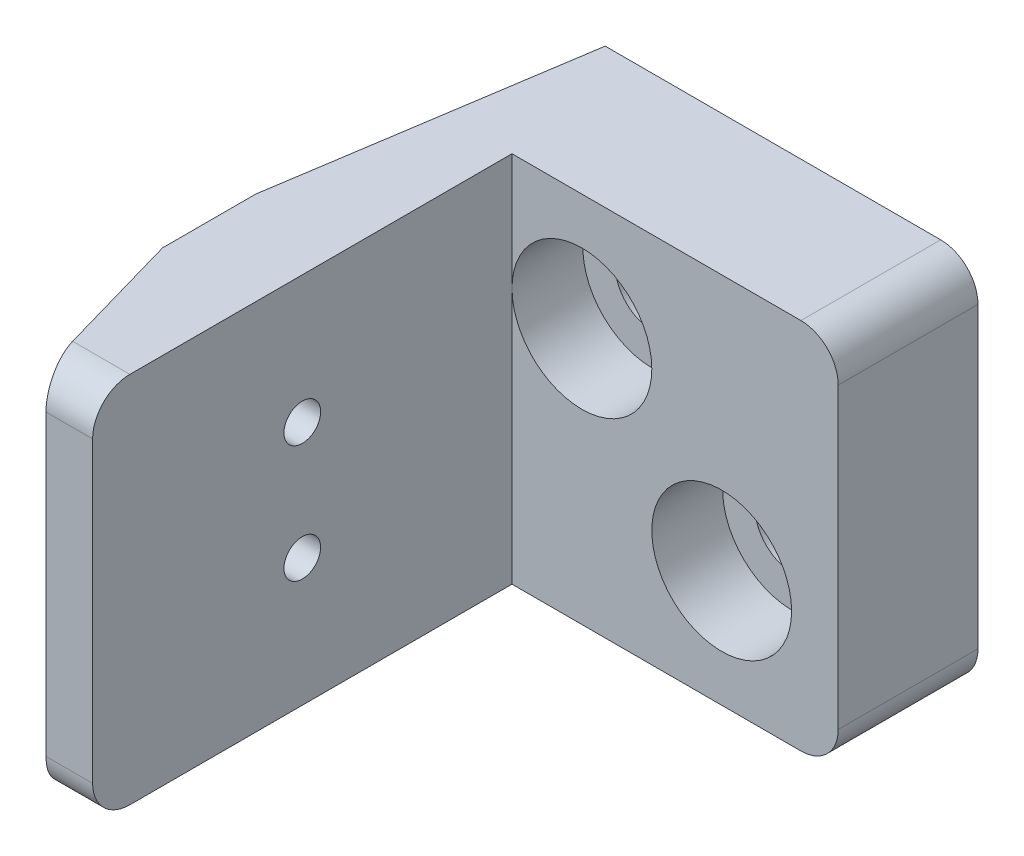
SolidWorks part; units mm, degrees
material "PET"
ref_plane "Front" through (0, 0, 0) normal (0, 0, 1) x (1, 0, 0)
ref_plane "Top" through (0, 0, 0) normal (0, 1, 0) x (1, 0, 0)
ref_plane "Right" through (0, 0, 0) normal (1, 0, 0) x (0, 0, -1)
sketch "Sketch1" plane through (0, 0, 0) normal (0, 1, 0) x (1, 0, 0)
  line L0 (0, 0) -> (22.225, 0)
  line L1 (22.225, 0) -> (22.225, 9.525)
  line L2 (22.225, 9.525) -> (-3.175, 9.525)
  line L4 (-3.175, -28.575) -> (0, -28.575)
  line L5 (0, -28.575) -> (0, 0)
  line L6 (-6.35, -11.1125) -> (-6.35, -17.4625)
  line L7 (-6.35, -17.4625) -> (-3.175, -28.575)
  line L8 (-6.35, -11.1125) -> (-3.175, 9.525)
  line L9 (-6.35, -14.2875) -> (0, -14.2875) construction
  point P9 (-2.7971, 3.81)
  point P10 (0, 0)
  point P11 (0, 0)
  point P14 (0, 0)
  dimension "D1" = 9.525
  dimension "D2" = 25.4
  dimension "D3" = 6.35
  dimension "D4" = 28.575
  dimension "D5" = 6.35
  dimension "D6" = 3.175
extrude "Boss-Extrude1" add sketch "Sketch1" along normal blind 25.4
sketch "Sketch4" plane through (0, 0, 0) normal (0, 0, 1) x (1, 0, 0)
  line L0 (-3.175, 25.4) -> (4.7625, 17.4625) construction
  line L1 (4.7625, 17.4625) -> (14.2875, 7.9375) construction
  line L2 (14.2875, 7.9375) -> (22.225, 0) construction
  point P0 (4.7625, 17.4625)
  point P2 (14.2875, 7.9375)
  point P19 (-5.1074, 28.4884)
  dimension "D1" = 9.525
hole_wizard "CBORE for #10 Socket Head Cap Screw1" positions "Sketch4" profile "Sketch5" counterbore size "#10" standard "ANSI Inch" end condition through all
sketch "Sketch5" plane through (4.7625, 17.4625, 0) normal (1, 0, 0) x (0, -1, 0)
  line L0 (0, 0) -> (0, 9.525)
  line L1 (0, 9.525) -> (2.5527, 9.525)
  line L3 (2.5527, 9.525) -> (2.5527, 4.826)
  line L4 (2.5527, 4.826) -> (4.7625, 4.826)
  line L5 (4.7625, 4.826) -> (4.7625, 0)
  line L7 (4.7625, 0) -> (0, 0)
  line L11 (0, -6.35) -> (0, 107.95) construction
  dimension "Thru Hole Dia." = 5.1054
  dimension "Thru Hole Depth" = 9.525
  dimension "C'Bore Dia." = 9.525
  dimension "C'Bore Depth" = 4.826
sketch "Sketch8" plane through (0, 0, 0) normal (1, 0, 0) x (0, 0, -1)
  line L2 (-14.2875, 8.7) -> (0, 0) construction
  line L3 (-28.575, 25.4) -> (-14.2875, 16.7) construction
  point P0 (-14.2875, 16.7)
  point P2 (-14.2875, 8.7)
  dimension "D1" = 8
hole_wizard "M3x0.5 Tapped Hole1" positions "Sketch8" profile "Sketch7" tap size "M3x0.5" standard "ANSI Metric" end condition through all
sketch "Sketch7" plane through (0, 16.7, 14.2875) normal (0, 1, 0) x (0, 0, -1)
  line L0 (0, 0) -> (0, 6.35)
  line L1 (0, 6.35) -> (1.25, 6.35)
  line L2 (1.25, 6.35) -> (1.25, 0)
  line L5 (1.25, 0) -> (0, 0)
  line L11 (0, -6.35) -> (0, 107.95) construction
  dimension "Thru Tap Drill Dia." = 2.5
  dimension "Thru Tap Drill Depth" = 6.35
cosmetic thread "Hole Thread1" parameters "D2"=3
cosmetic thread "Hole Thread2" parameters "D2"=3
fillet "Fillet1" radius 2.54 4 edges at (-1.5875, 0, 28.575) (-1.5875, 25.4, 28.575) (22.225, 0, -4.7625) (22.225, 25.4, -4.7625)
